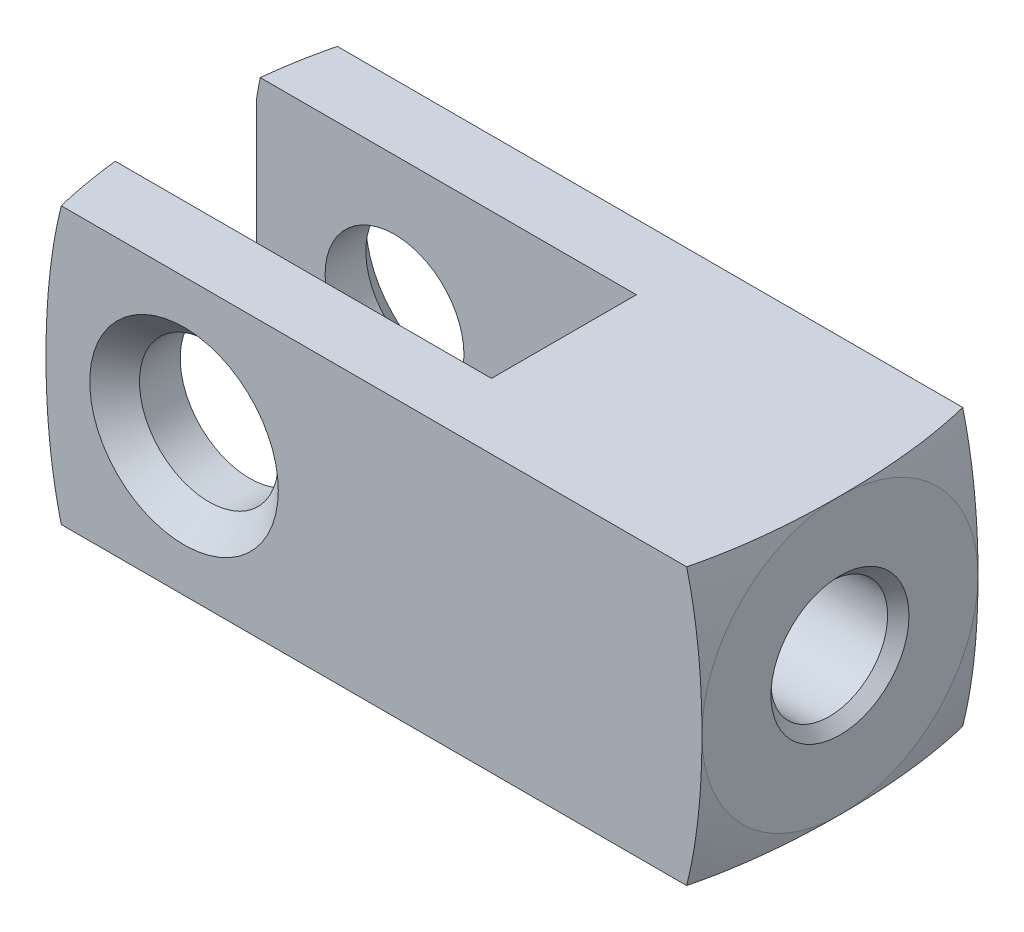
SolidWorks part; units mm, degrees
material "Cast Alloy Steel"
ref_plane "Front Plane" through (0, 0, 0) normal (0, 0, 1) x (1, 0, 0)
ref_plane "Top Plane" through (0, 0, 0) normal (0, 1, 0) x (1, 0, 0)
ref_plane "Right Plane" through (0, 0, 0) normal (1, 0, 0) x (0, 0, -1)
sketch "Sketch1" plane through (0, 0, 0) normal (0, 0, 1) x (1, 0, 0)
  line L0 (-6.35, 6.35) -> (-6.35, -6.35)
  line L1 (-6.35, -6.35) -> (23.8252, -6.35)
  line L2 (23.8252, -6.35) -> (23.8252, 6.35)
  line L3 (23.8252, 6.35) -> (-6.35, 6.35)
extrude "Boss-Extrude1" add sketch "Sketch1" against normal blind 6.35 and the other way blind 6.35
sketch "Sketch2" plane through (0, 0, 0) normal (0, 1, 0) x (1, 0, 0)
  line L0 (-6.35, 3.3338) -> (-6.35, -3.3338)
  line L1 (-6.35, -3.3338) -> (11.1252, -3.3338)
  line L2 (11.1252, -3.3338) -> (11.1252, 3.3338)
  line L3 (11.1252, 3.3338) -> (-6.35, 3.3338)
extrude "Cut-Extrude1" cut sketch "Sketch2" along normal blind 6.35 and the other way blind 6.35
hole_wizard "Hole1" positions "Sketch4" profile "Sketch3" legacy
sketch "Sketch4" plane through (23.8252, 0, 0) normal (1, 0, 0) x (0, 0, -1)
  point P0 (0, 0)
sketch "Sketch3" plane through (23.8252, 0, 0) normal (0, 1, 0) x (0, 0, -1)
  line L0 (0, 0) -> (0, 11.176)
  line L1 (0, 11.176) -> (2.6835, 11.176)
  line L2 (2.6835, 11.176) -> (2.6835, 0.4915)
  line L3 (2.6835, 0.4915) -> (3.175, 0)
  line L4 (3.175, 0) -> (0, 0)
  line L5 (0, -6.4453) -> (0, 115.525) construction
  line L6 (-2.6835, 0.4915) -> (-3.175, 0) construction
  dimension "Diameter" = 5.367
  dimension "Depth" = 11.176
  dimension "C-Sink Angle" = 90
  dimension "C-Sink Diameter" = 6.35
cosmetic thread "Cosmetic Thread1" parameters "D1"=11.176, "D2"=6.35
ref_plane "Plane1" through (0, 0, 6.35) normal (0, 0, 1) x (1, 0, 0)
ref_plane "Plane2" through (0, 0, -6.35) normal (0, 0, 1) x (1, 0, 0)
ref_plane "Plane3" through (23.876, 0, 0) normal (1, 0, 0) x (0, 0, -1)
hole_wizard "Hole2" positions "Sketch6" profile "Sketch5" legacy
sketch "Sketch6" plane through (12.6492, 0, 0) normal (1, 0, 0) x (0, 0, -1)
  point P0 (0, 0)
sketch "Sketch5" plane through (12.6492, 0, 0) normal (0, 1, 0) x (0, 0, -1)
  line L0 (0, 0) -> (0, 1.524)
  line L1 (0, 1.524) -> (2.7051, 1.524)
  line L2 (2.7051, 1.524) -> (2.7051, 0)
  line L3 (2.7051, 0) -> (0, 0)
  line L4 (0, 110) -> (0, -10) construction
  dimension "Diameter" = 5.4102
  dimension "Depth" = 1.524
sketch "Sketch7" plane through (0, 0, 0) normal (1, 0, 0) x (0, 0, -1)
  line L0 (-6.35, 0) -> (-6.35, 4.337)
  line L1 (-6.35, 4.337) -> (-5.207, 3.194)
  line L2 (-5.207, 3.194) -> (5.207, 3.194)
  line L3 (5.207, 3.194) -> (6.35, 4.337)
  line L4 (6.35, 4.337) -> (6.35, 0)
  line L5 (6.35, 0) -> (-6.35, 0)
  line L6 (6.35, 0) -> (-6.35, 0) construction
revolve "Cut-Revolve1" cut sketch "Sketch7" angle 360 about L6 reverse direction yes
sketch "Sketch8" plane through (0, 0, 0) normal (0, 0, 1) x (1, 0, 0)
  line L0 (23.8252, 0) -> (23.8252, 6.35)
  line L1 (21.2852, 12.7) -> (30.1752, 12.7)
  line L2 (30.1752, 12.7) -> (30.1752, 0)
  line L3 (30.1752, 0) -> (23.8252, 0)
  line L4 (30.1752, 0) -> (23.8252, 0) construction
  arc A0 (23.8252, 6.35) -> (21.2852, 12.7) centre (6.6802, 3.175) ccw
revolve "Cut-Revolve2" cut sketch "Sketch8" angle 360 about L4 reverse direction yes
sketch "Sketch9" plane through (0, 0, 0) normal (0, 0, 1) x (1, 0, 0)
  line L0 (-12.7, 0) -> (-12.7, 12.7)
  line L1 (-12.7, 12.7) -> (-3.81, 12.7)
  line L2 (-6.35, 6.35) -> (-6.35, 0)
  line L3 (-6.35, 0) -> (-12.7, 0)
  line L4 (-6.35, 0) -> (-12.7, 0) construction
  arc A0 (-3.81, 12.7) -> (-6.35, 6.35) centre (10.795, 3.175) ccw
revolve "Cut-Revolve3" cut sketch "Sketch9" angle 360 about L4 reverse direction yes
ref_plane "Plane4" through (23.8252, 0, 0) normal (1, 0, 0) x (0, 0, -1)
ref_plane "Plane5" through (11.1252, 0, 0) normal (1, 0, 0) x (0, 0, -1)
ref_plane "dummy XY" through (0, 0, 0) normal (0, 0, 1) x (1, 0, 0)
ref_plane "dummy XZ" through (0, 0, 0) normal (0, -1, 0) x (-1, 0, 0)
ref_plane "dummy YZ" through (0, 0, 0) normal (1, 0, 0) x (0, 0, -1)
ref_axis "dummy X" through (-80.9, 0, 0) along (1, 0, 0)
ref_axis "dummy Y" through (0, -50, 0) along (0, 1, 0)
ref_axis "dummy Z" through (0, 0, 80.9) along (0, 0, -1)
sketch3d "dummy"
  point P0 (0, 0, 0)
ref_plane "h1 XY" through (0, 0, 0) normal (0, 0, 1) x (1, 0, 0)
ref_plane "h1 XZ" through (0, 6.35, 0) normal (0, -1, 0) x (-1, 0, 0)
ref_plane "h1 YZ" through (-6.35, 0, 0) normal (1, 0, 0) x (0, 0, -1)
ref_axis "h1 X" through (-80.9, 6.35, 0) along (1, 0, 0)
ref_axis "h1 Y" through (-6.35, -50, 0) along (0, 1, 0)
ref_axis "h1 Z" through (-6.35, 6.35, 80.9) along (0, 0, -1)
sketch3d "h1"
  point P0 (-6.35, 6.35, 0)
ref_plane "h2 XY" through (0, 0, 0) normal (0, 0, 1) x (1, 0, 0)
ref_plane "h2 XZ" through (0, -6.35, 0) normal (0, -1, 0) x (-1, 0, 0)
ref_plane "h2 YZ" through (-6.35, 0, 0) normal (1, 0, 0) x (0, 0, -1)
ref_axis "h2 X" through (-80.9, -6.35, 0) along (1, 0, 0)
ref_axis "h2 Y" through (-6.35, -50, 0) along (0, 1, 0)
ref_axis "h2 Z" through (-6.35, -6.35, 80.9) along (0, 0, -1)
sketch3d "h2"
  point P0 (-6.35, -6.35, 0)
ref_plane "l1 XY" through (0, 0, 0) normal (0, 0, 1) x (1, 0, 0)
ref_plane "l1 XZ" through (0, 6.35, 0) normal (0, -1, 0) x (-1, 0, 0)
ref_plane "l1 YZ" through (23.8252, 0, 0) normal (1, 0, 0) x (0, 0, -1)
ref_axis "l1 X" through (-80.9, 6.35, 0) along (1, 0, 0)
ref_axis "l1 Y" through (23.8252, -50, 0) along (0, 1, 0)
ref_axis "l1 Z" through (23.8252, 6.35, 80.9) along (0, 0, -1)
sketch3d "l1"
  point P0 (23.8252, 6.35, 0)
ref_plane "l11 XY" through (0, 0, 0) normal (0, 0, 1) x (1, 0, 0)
ref_plane "l11 XZ" through (0, 6.35, 0) normal (0, -1, 0) x (-1, 0, 0)
ref_plane "l11 YZ" through (23.8252, 0, 0) normal (1, 0, 0) x (0, 0, -1)
ref_axis "l11 X" through (-80.9, 6.35, 0) along (1, 0, 0)
ref_axis "l11 Y" through (23.8252, -50, 0) along (0, 1, 0)
ref_axis "l11 Z" through (23.8252, 6.35, 80.9) along (0, 0, -1)
sketch3d "l11"
  point P0 (23.8252, 6.35, 0)
ref_plane "l12 XY" through (0, 0, 0) normal (0, 0, 1) x (1, 0, 0)
ref_plane "l12 XZ" through (0, 6.35, 0) normal (0, -1, 0) x (-1, 0, 0)
ref_plane "l12 YZ" through (0, 0, 0) normal (1, 0, 0) x (0, 0, -1)
ref_axis "l12 X" through (-80.9, 6.35, 0) along (1, 0, 0)
ref_axis "l12 Y" through (0, -50, 0) along (0, 1, 0)
ref_axis "l12 Z" through (0, 6.35, 80.9) along (0, 0, -1)
sketch3d "l12"
  point P0 (0, 6.35, 0)
ref_plane "l2 XY" through (0, 0, 0) normal (0, 0, 1) x (1, 0, 0)
ref_plane "l2 XZ" through (0, 6.35, 0) normal (0, -1, 0) x (-1, 0, 0)
ref_plane "l2 YZ" through (-6.35, 0, 0) normal (1, 0, 0) x (0, 0, -1)
ref_axis "l2 X" through (-80.9, 6.35, 0) along (1, 0, 0)
ref_axis "l2 Y" through (-6.35, -50, 0) along (0, 1, 0)
ref_axis "l2 Z" through (-6.35, 6.35, 80.9) along (0, 0, -1)
sketch3d "l2"
  point P0 (-6.35, 6.35, 0)
ref_plane "l21 XY" through (0, 0, 0) normal (0, 1, 0) x (1, 0, 0)
ref_plane "l21 XZ" through (0, 0, 0) normal (0, 0, 1) x (1, 0, 0)
ref_plane "l21 YZ" through (23.8252, 0, 0) normal (1, 0, 0) x (0, 0, -1)
ref_axis "l21 X" through (-80.9, 0, 0) along (1, 0, 0)
ref_axis "l21 Y" through (23.8252, 0, 50) along (0, 0, -1)
ref_axis "l21 Z" through (23.8252, 50, 0) along (0, -1, 0)
sketch3d "l21"
  point P0 (23.8252, 0, 0)
ref_plane "l22 XY" through (0, 0, 0) normal (0, 1, 0) x (1, 0, 0)
ref_plane "l22 XZ" through (0, 0, 0) normal (0, 0, 1) x (1, 0, 0)
ref_plane "l22 YZ" through (11.1252, 0, 0) normal (1, 0, 0) x (0, 0, -1)
ref_axis "l22 X" through (-80.9, 0, 0) along (1, 0, 0)
ref_axis "l22 Y" through (11.1252, 0, 50) along (0, 0, -1)
ref_axis "l22 Z" through (11.1252, 50, 0) along (0, -1, 0)
sketch3d "l22"
  point P0 (11.1252, 0, 0)
ref_plane "piston_rod_clevis XY" through (23.8252, 0, 0) normal (1, 0, 0) x (0, 0, -1)
ref_plane "piston_rod_clevis XZ" through (0, 0, 0) normal (0, -1, 0) x (-1, 0, 0)
ref_plane "piston_rod_clevis YZ" through (0, 0, 0) normal (0, 0, -1) x (-1, 0, 0)
ref_axis "piston_rod_clevis X" through (23.8252, 0, 80.9) along (0, 0, -1)
ref_axis "piston_rod_clevis Y" through (23.8252, -50, 0) along (0, 1, 0)
ref_axis "piston_rod_clevis Z" through (80.9, 0, 0) along (-1, 0, 0)
sketch3d "piston_rod_clevis"
  point P0 (23.8252, 0, 0)
ref_plane "rod_clevis_body XY" through (0, 0, 0) normal (0, 0, 1) x (1, 0, 0)
ref_plane "rod_clevis_body XZ" through (0, 0, 0) normal (0, -1, 0) x (-1, 0, 0)
ref_plane "rod_clevis_body YZ" through (0, 0, 0) normal (1, 0, 0) x (0, 0, -1)
ref_axis "rod_clevis_body X" through (-80.9, 0, 0) along (1, 0, 0)
ref_axis "rod_clevis_body Y" through (0, -50, 0) along (0, 1, 0)
ref_axis "rod_clevis_body Z" through (0, 0, 80.9) along (0, 0, -1)
sketch3d "rod_clevis_body"
  point P0 (0, 0, 0)
ref_plane "th1 XY" through (0, 0, 0) normal (0, 0, 1) x (1, 0, 0)
ref_plane "th1 XZ" through (0, 3.175, 0) normal (0, -1, 0) x (-1, 0, 0)
ref_plane "th1 YZ" through (23.8252, 0, 0) normal (1, 0, 0) x (0, 0, -1)
ref_axis "th1 X" through (-80.9, 3.175, 0) along (1, 0, 0)
ref_axis "th1 Y" through (23.8252, -50, 0) along (0, 1, 0)
ref_axis "th1 Z" through (23.8252, 3.175, 80.9) along (0, 0, -1)
sketch3d "th1"
  point P0 (23.8252, 3.175, 0)
ref_plane "th2 XY" through (0, 0, 0) normal (0, 0, 1) x (1, 0, 0)
ref_plane "th2 XZ" through (0, -3.175, 0) normal (0, -1, 0) x (-1, 0, 0)
ref_plane "th2 YZ" through (23.8252, 0, 0) normal (1, 0, 0) x (0, 0, -1)
ref_axis "th2 X" through (-80.9, -3.175, 0) along (1, 0, 0)
ref_axis "th2 Y" through (23.8252, -50, 0) along (0, 1, 0)
ref_axis "th2 Z" through (23.8252, -3.175, 80.9) along (0, 0, -1)
sketch3d "th2"
  point P0 (23.8252, -3.175, 0)
ref_plane "to_cylinder XY" through (11.1252, 0, 0) normal (1, 0, 0) x (0, 0, -1)
ref_plane "to_cylinder XZ" through (0, 0, 0) normal (0, -1, 0) x (-1, 0, 0)
ref_plane "to_cylinder YZ" through (0, 0, 0) normal (0, 0, -1) x (-1, 0, 0)
ref_axis "to_cylinder X" through (11.1252, 0, 80.9) along (0, 0, -1)
ref_axis "to_cylinder Y" through (11.1252, -50, 0) along (0, 1, 0)
ref_axis "to_cylinder Z" through (80.9, 0, 0) along (-1, 0, 0)
sketch3d "to_cylinder"
  point P0 (11.1252, 0, 0)
ref_plane "w1 XY" through (0, 0, 0) normal (0, 1, 0) x (1, 0, 0)
ref_plane "w1 XZ" through (0, 0, -6.35) normal (0, 0, 1) x (1, 0, 0)
ref_plane "w1 YZ" through (23.8252, 0, 0) normal (1, 0, 0) x (0, 0, -1)
ref_axis "w1 X" through (-80.9, 0, -6.35) along (1, 0, 0)
ref_axis "w1 Y" through (23.8252, 0, 50) along (0, 0, -1)
ref_axis "w1 Z" through (23.8252, 50, -6.35) along (0, -1, 0)
sketch3d "w1"
  point P0 (23.8252, 0, -6.35)
ref_plane "w11 XY" through (0, 0, 0) normal (0, 1, 0) x (1, 0, 0)
ref_plane "w11 XZ" through (0, 0, -3.3338) normal (0, 0, 1) x (1, 0, 0)
ref_plane "w11 YZ" through (-6.35, 0, 0) normal (1, 0, 0) x (0, 0, -1)
ref_axis "w11 X" through (-80.9, 0, -3.3338) along (1, 0, 0)
ref_axis "w11 Y" through (-6.35, 0, 50) along (0, 0, -1)
ref_axis "w11 Z" through (-6.35, 50, -3.3338) along (0, -1, 0)
sketch3d "w11"
  point P0 (-6.35, 0, -3.3338)
ref_plane "w12 XY" through (0, 0, 0) normal (0, 1, 0) x (1, 0, 0)
ref_plane "w12 XZ" through (0, 0, 3.3338) normal (0, 0, 1) x (1, 0, 0)
ref_plane "w12 YZ" through (-6.35, 0, 0) normal (1, 0, 0) x (0, 0, -1)
ref_axis "w12 X" through (-80.9, 0, 3.3338) along (1, 0, 0)
ref_axis "w12 Y" through (-6.35, 0, 50) along (0, 0, -1)
ref_axis "w12 Z" through (-6.35, 50, 3.3338) along (0, -1, 0)
sketch3d "w12"
  point P0 (-6.35, 0, 3.3338)
ref_plane "w2 XY" through (0, 0, 0) normal (0, 1, 0) x (1, 0, 0)
ref_plane "w2 XZ" through (0, 0, 6.35) normal (0, 0, 1) x (1, 0, 0)
ref_plane "w2 YZ" through (23.8252, 0, 0) normal (1, 0, 0) x (0, 0, -1)
ref_axis "w2 X" through (-80.9, 0, 6.35) along (1, 0, 0)
ref_axis "w2 Y" through (23.8252, 0, 50) along (0, 0, -1)
ref_axis "w2 Z" through (23.8252, 50, 6.35) along (0, -1, 0)
sketch3d "w2"
  point P0 (23.8252, 0, 6.35)
